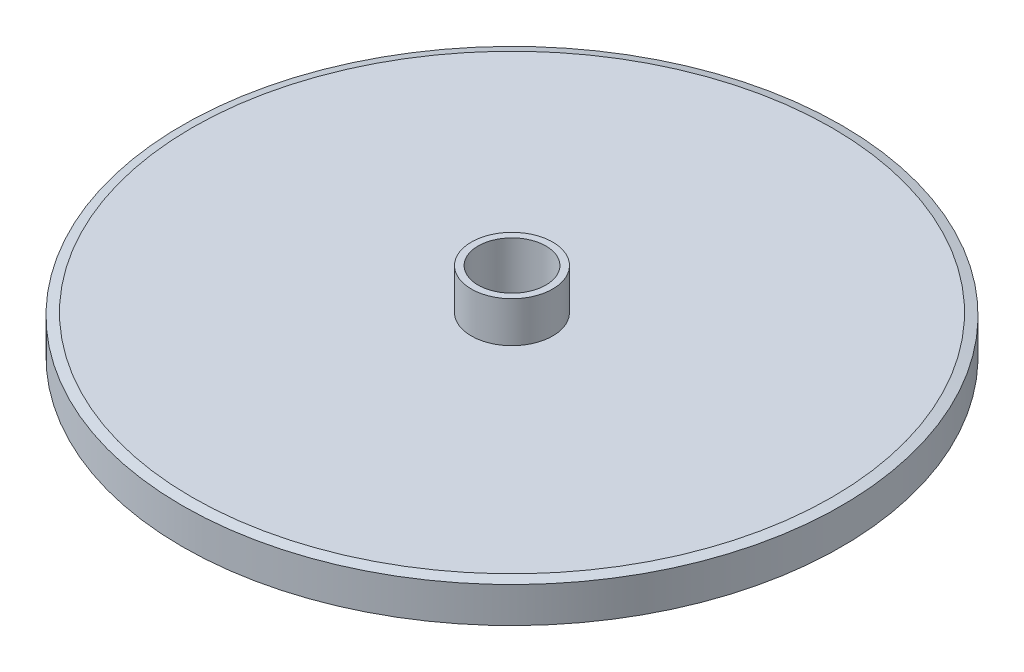
SolidWorks part; units mm, degrees
material "Сталь ШХ15 ГОСТ 801-78"
ref_plane "Plane1" through (0, 0, 0) normal (0, 0, 1) x (1, 0, 0)
ref_plane "Plane2" through (0, 0, 0) normal (0, 1, 0) x (1, 0, 0)
ref_plane "Plane3" through (0, 0, 0) normal (1, 0, 0) x (0, 0, -1)
sketch "Эскиз1" plane through (0, 0, 0) normal (0, 0, 1) x (1, 0, 0)
  line L0 (0, 0) -> (24.3, 0)
  line L1 (24.3, 0) -> (24.3, 3)
  line L2 (24.3, 3) -> (3, 3)
  line L3 (3, 3) -> (3, 6)
  line L4 (3, 6) -> (0, 6)
  line L5 (0, 6) -> (0, 0)
  dimension "D1" = 3
  dimension "30" = 24.3
  dimension "D3" = 3
  dimension "D4" = 3
ref_axis "Ось1" through (0, 6, 0) along (0, -1, 0)
revolve "Повернуть2" add sketch "Эскиз1" angle 360 about axis through (0, 6, 0) along (0, -1, 0)
chamfer "Фаска1" distance 0.705 angle 15 1 edges at (0, 3, 24.3) first distance on face at (0, 3, 3)
sketch "Эскиз2" plane through (0, 0, 0) normal (0, -1, 0) x (-1, 0, 0)
  circle A0 centre (0, 0) radius 2.5
extrude "Вырез-Вытянуть3" cut sketch "Эскиз2" against normal through all both
chamfer "Фаска2" distance 0.705 angle 15 1 edges at (0, 0, 24.3) first distance on face at (0, 0, -2.5)
